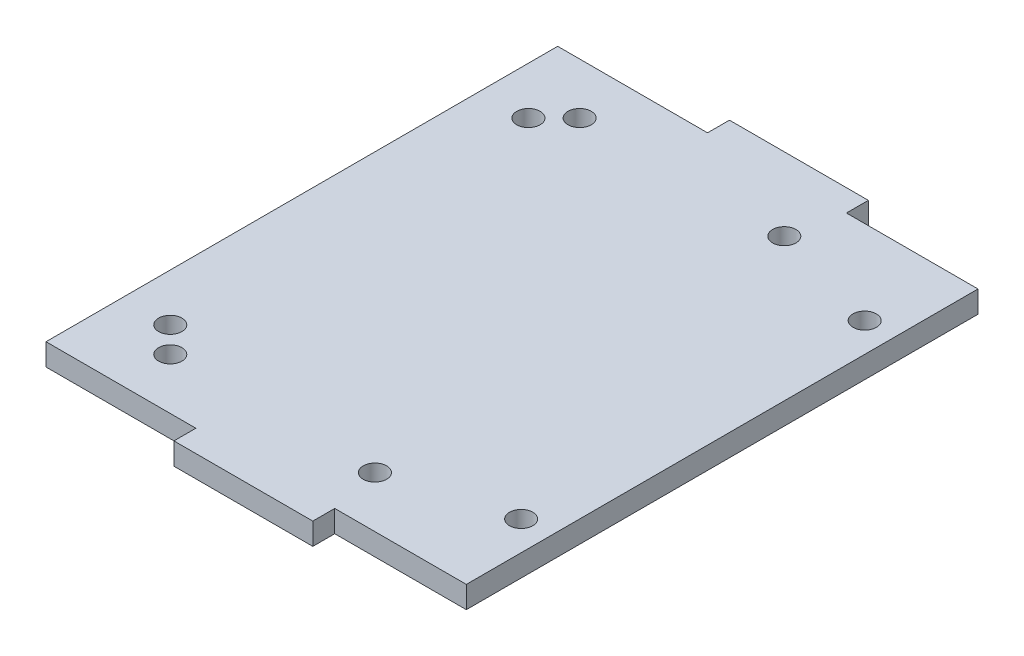
SolidWorks part; units mm, degrees
ref_plane "Front Plane" through (0, 0, 0) normal (0, 0, 1) x (1, 0, 0)
ref_plane "Top Plane" through (0, 0, 0) normal (0, 1, 0) x (1, 0, 0)
ref_plane "Right Plane" through (0, 0, 0) normal (1, 0, 0) x (0, 0, -1)
sketch "Sketch1" plane through (0, 0, 0) normal (0, 1, 0) x (1, 0, 0)
  line L0 (63.7979, -35) -> (63.7979, 35)
  line L1 (8.7979, 35) -> (6.2979, 35)
  line L2 (6.2979, 35) -> (6.2979, -35)
  line L3 (6.2979, -35) -> (8.7979, -35)
  line L7 (8.7979, 35) -> (26.7979, 35)
  line L8 (26.7979, 35) -> (26.7979, 38)
  line L9 (26.7979, 38) -> (45.7979, 38)
  line L10 (45.7979, 38) -> (45.7979, 35)
  line L11 (45.7979, 35) -> (63.7979, 35)
  line L13 (0, 0) -> (58, 0) construction
  line L18 (61, -35) -> (63.7979, -35)
  line L19 (61, 35) -> (63.7979, 35)
  line L25 (36.2979, -34.5) -> (36.2979, 34.5) construction
  line L31 (9.2979, 34.5) -> (63.2979, -34.5) construction
  line L32 (9.2979, -34.5) -> (63.2979, 34.5) construction
  line L37 (61, -35) -> (63.7979, -35)
  line L38 (45.7979, -35) -> (63.7979, -35)
  line L39 (45.7979, -38) -> (45.7979, -35)
  line L40 (26.7979, -38) -> (45.7979, -38)
  line L41 (26.7979, -35) -> (26.7979, -38)
  line L42 (8.7979, -35) -> (26.7979, -35)
  circle A0 centre (12.7979, -24.5) radius 1.6
  circle A1 centre (59.7979, -23.5) radius 1.6
  circle A2 centre (16.2979, 28) radius 1.6
  circle A3 centre (44.2979, 28) radius 1.6
  circle A4 centre (44.2979, -28) radius 1.6
  circle A5 centre (16.2979, -28) radius 1.6
  circle A6 centre (59.7979, 23.5) radius 1.6
  circle A7 centre (12.7979, 24.5) radius 1.6
  point P29 (36.2979, 0)
  dimension "D14" = 3.2
  dimension "D17" = 3.2
  dimension "D18" = 3.2
  dimension "D19" = 3.2
  dimension "D8" = 28
  dimension "D3" = 47
  dimension "D4" = 19
  dimension "D5" = 18
  dimension "D6" = 26.7979
  dimension "D7" = 18
  dimension "D9" = 52.5
  dimension "D10" = 51.5
  dimension "D11" = 3
  dimension "D12" = 69
  dimension "D13" = 7
  dimension "D15" = 2.5
  dimension "D16" = 3.5
  dimension "D23" = 19
extrude "Boss-Extrude1" add sketch "Sketch1" along normal blind 3 contours L42 L41 L40 L39 L38 L18 L19 L11 L10 L9 L8 L7 | A3 A2 A1 A0 region at (35.1105, 0, 0)
